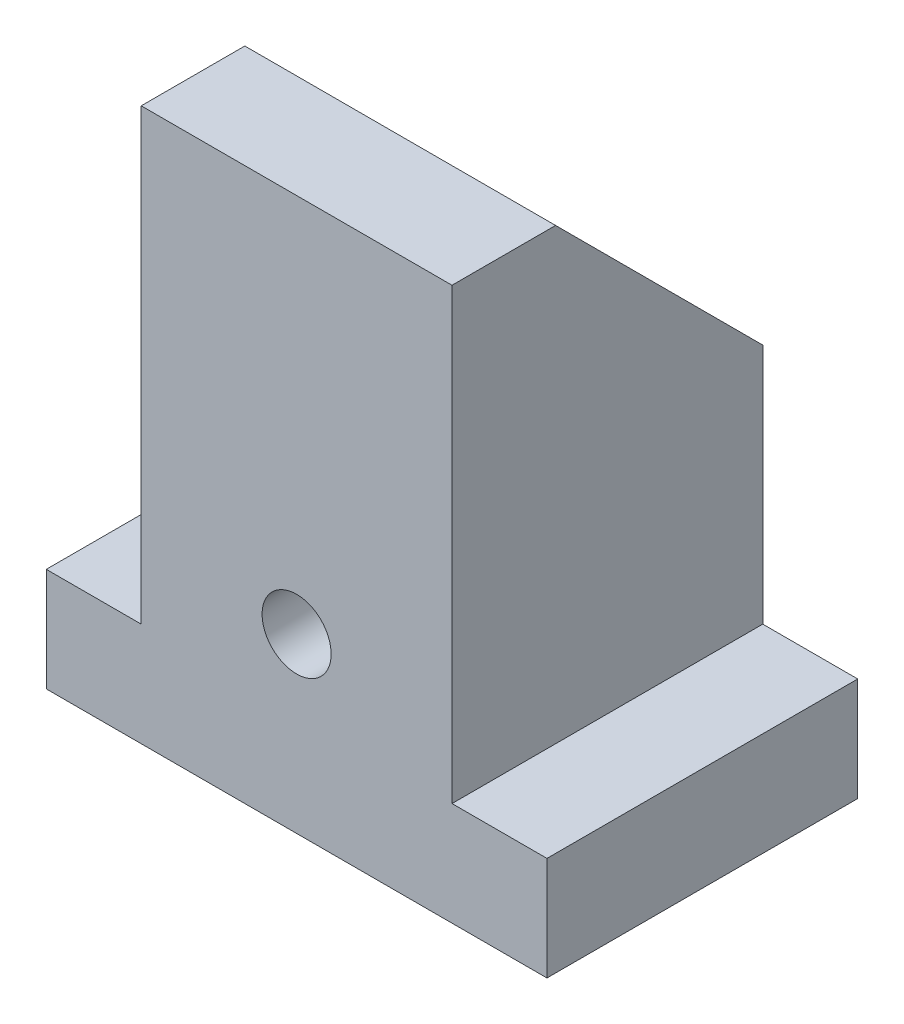
SolidWorks part; units mm, degrees
ref_plane "Ebene vorne" through (0, 0, 0) normal (0, 0, 1) x (1, 0, 0)
ref_plane "Ebene oben" through (0, 0, 0) normal (0, 1, 0) x (1, 0, 0)
ref_plane "Ebene rechts" through (0, 0, 0) normal (1, 0, 0) x (0, 0, -1)
sketch "Sketch1" plane through (0, 0, 0) normal (0, 1, 0) x (1, 0, 0)
  line L1 (0, 0) -> (9, 0)
  line L2 (0, 0) -> (0, 9)
  line L3 (0, 9) -> (9, 9)
  line L4 (9, 0) -> (9, 9)
  dimension "D1" = 9
  dimension "D2" = 9
extrude "Boss-Extrude1" add sketch "Sketch1" along normal blind 16
fillet "Chamfer1" radius 6 1 edges at (4.5, 16, -9) profile chamfer
sketch "Sketch2" plane through (0, 0, 0) normal (0, -1, 0) x (1, 0, 0)
  line L0 (9, -4.5) -> (0, -4.5) construction
  line L1 (9, 0) -> (9, -9) construction
  line L2 (0, -9) -> (0, 0) construction
  circle A0 centre (4.5, -4.5) radius 3.1
  dimension "D1" = 6.2
extrude "Cut-Extrude1" cut sketch "Sketch2" against normal blind 8
sketch "Sketch3" plane through (0, 0, -9) normal (0, 0, -1) x (-1, 0, 0)
  line L0 (-4.5, 0) -> (-4.5, 10) construction
  line L1 (-9, 0) -> (0, 0) construction
  line L2 (0, 10) -> (-9, 10) construction
  line L3 (-7.6, 8) -> (-1.4, 8) construction
  line L4 (-7.6, 8) -> (-1.4, 8) construction
  circle A0 centre (-4.5, 5) radius 1
  dimension "D1" = 2
  dimension "D2" = 3
extrude "Cut-Extrude2" cut sketch "Sketch3" against normal up to surface (9 mm away) up to face at (4.5, 8, 0)
sketch "Sketch4" plane through (0, 0, 0) normal (0, -1, 0) x (-1, 0, 0)
  line L0 (-4.5, 9) -> (-4.5, 0) construction
  line L11 (-9, 0) -> (-11.75, 0)
  line L12 (-9, 0) -> (-9, 9)
  line L13 (-9, 9) -> (-11.75, 9)
  line L14 (-11.75, 0) -> (-11.75, 9)
  line L15 (-9, 9) -> (0, 9) construction
  line L16 (0, 0) -> (-9, 0) construction
  line L17 (2.75, 0) -> (2.75, 9)
  line L18 (0, 9) -> (2.75, 9)
  line L19 (0, 0) -> (0, 9)
  line L20 (0, 0) -> (2.75, 0)
  dimension "D1" = 14.5
extrude "Boss-Extrude2" add sketch "Sketch4" against normal blind 3
